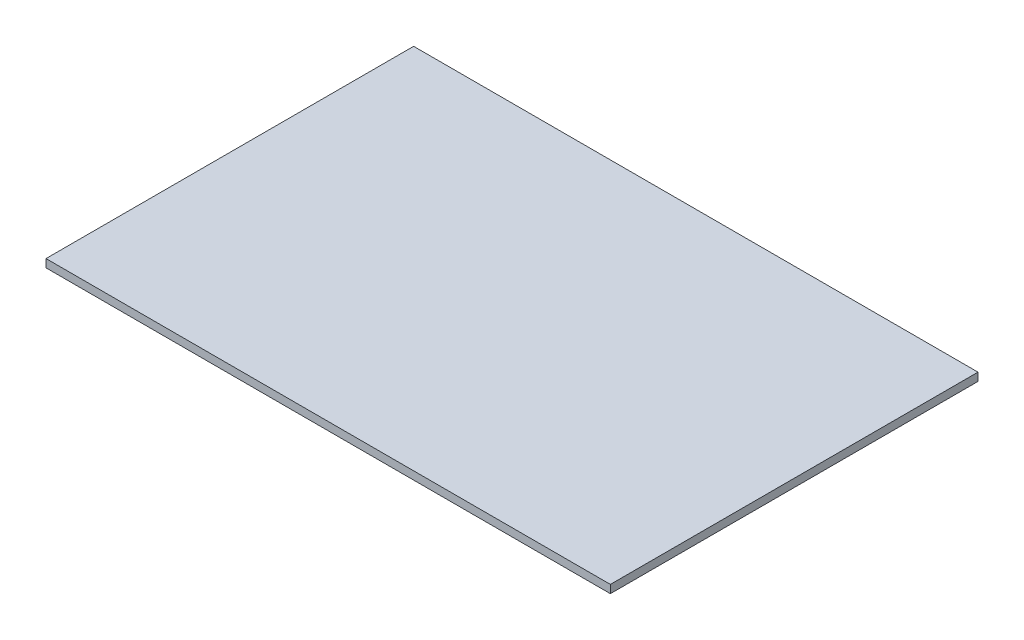
SolidWorks part; units mm, degrees
material "A-Glass Fiber"
ref_plane "Front Plane" through (0, 0, 0) normal (0, 0, 1) x (1, 0, 0)
ref_plane "Top Plane" through (0, 0, 0) normal (0, 1, 0) x (1, 0, 0)
ref_plane "Right Plane" through (0, 0, 0) normal (1, 0, 0) x (0, 0, -1)
sketch "Sketch1" plane through (0, 0, 0) normal (0, 1, 0) x (1, 0, 0)
  line L1 (0, 0) -> (111.125, 0)
  line L2 (0, 0) -> (0, 72.39)
  line L3 (0, 72.39) -> (111.125, 72.39)
  line L4 (111.125, 0) -> (111.125, 72.39)
  dimension "D1" = 111.125
  dimension "D2" = 72.39
extrude "Boss-Extrude1" add sketch "Sketch1" along normal blind 1.5875
sketch "Sketch2" plane through (0, 0, 0) normal (0, -1, 0) x (1, 0, 0)
  line L0 (0, -72.39) -> (0, 0) construction
  line L1 (0, -5.08) -> (111.125, -5.08)
  line L2 (0, -5.08) -> (0, -67.31)
  line L3 (0, -67.31) -> (111.125, -67.31)
  line L4 (111.125, -5.08) -> (111.125, -67.31)
  line L5 (111.125, 0) -> (111.125, -72.39) construction
  line L6 (0, 0) -> (111.125, 0) construction
  line L7 (111.125, -72.39) -> (0, -72.39) construction
  dimension "D1" = 5.08
  dimension "D2" = 5.08
